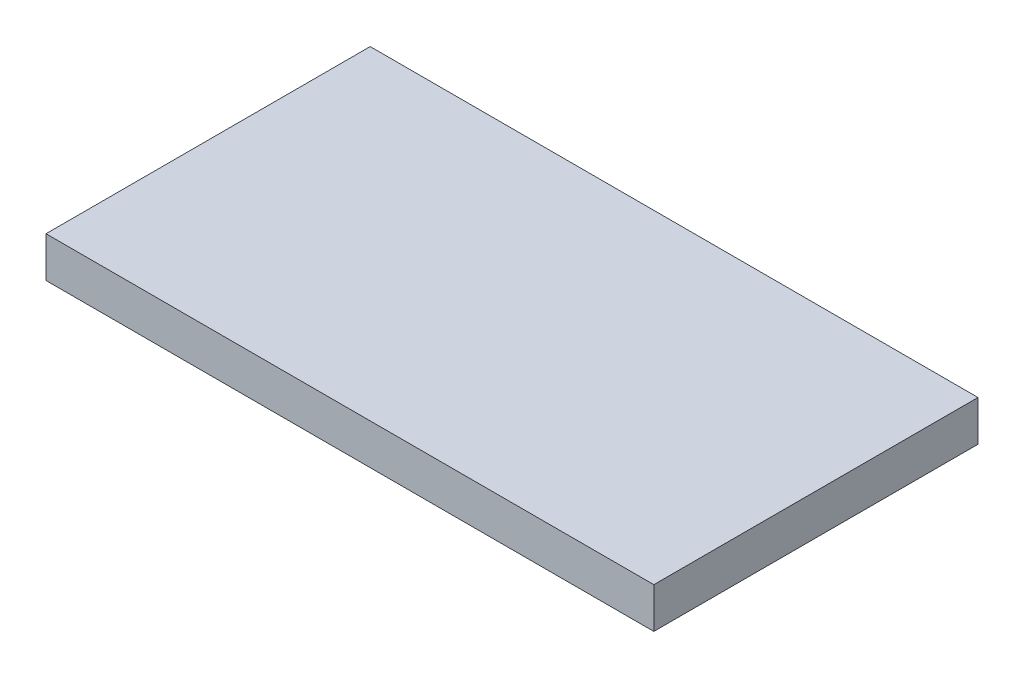
SolidWorks part; units mm, degrees
ref_plane "Alzado" through (0, 0, 0) normal (0, 0, 1) x (1, 0, 0)
ref_plane "Planta" through (0, 0, 0) normal (0, 1, 0) x (1, 0, 0)
ref_plane "Vista lateral" through (0, 0, 0) normal (1, 0, 0) x (0, 0, -1)
sketch "Croquis1" plane through (0, 0, 0) normal (0, 1, 0) x (1, 0, 0)
  line L1 (65, -30) -> (-65, -30)
  line L2 (65, -30) -> (65, 30)
  line L3 (65, 30) -> (-65, 30)
  line L4 (-65, -30) -> (-65, 30)
  line L5 (65, -30) -> (-65, 30) construction
  line L6 (65, 30) -> (-65, -30) construction
  line L7 (75, -40) -> (-75, -40)
  line L8 (75, -40) -> (75, 40)
  line L9 (75, 40) -> (-75, 40)
  line L10 (-75, -40) -> (-75, 40)
  line L11 (75, -40) -> (-75, 40) construction
  line L12 (75, 40) -> (-75, -40) construction
  point P0 (0, 0)
  point P6 (0, 0)
  dimension "D1" = 130
  dimension "D2" = 60
  dimension "D3" = 10
  dimension "D4" = 10
extrude "Saliente-Extruir1" add sketch "Croquis1" against normal blind 7.5 contours L4 L1 L2 L3 region at (0, 0, 0)
extrude "Saliente-Extruir2" add sketch "Croquis1<4>" along normal blind 10 contours L4 L1 L2 L3 | L10 L7 L8 L9 L1 L4 L3 L2 region at (0, 0, 0) region at (0, 0, 38.3)
sketch "Croquis1<4>" plane through (0, 0, 0) normal (0, 1, 0) x (1, 0, 0) same geometry as "Croquis1"
